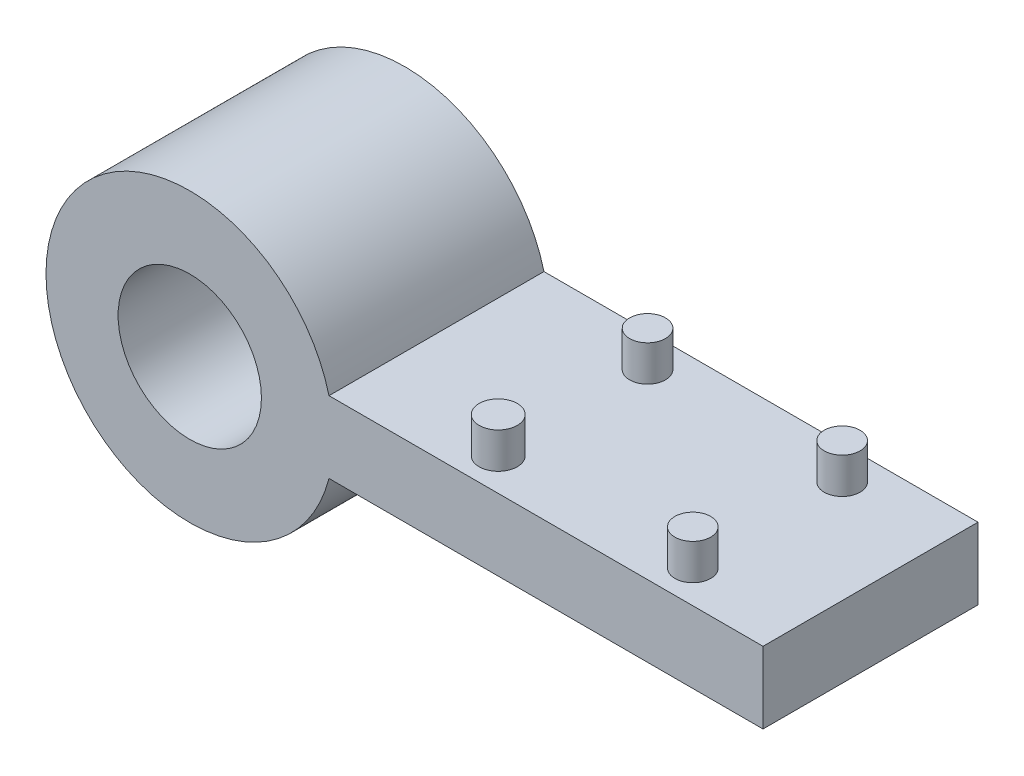
SolidWorks part; units mm, degrees
ref_plane "Front Plane" through (0, 0, 0) normal (0, 0, 1) x (1, 0, 0)
ref_plane "Top Plane" through (0, 0, 0) normal (0, 1, 0) x (1, 0, 0)
ref_plane "Right Plane" through (0, 0, 0) normal (1, 0, 0) x (0, 0, -1)
sketch "Sketch1" plane through (0, 0, -0.4159) normal (0, 1, 0) x (1, 0, 0)
  line L1 (-23.2517, 4.1989) -> (56.7483, 4.1989)
  line L2 (-23.2517, 4.1989) -> (-23.2517, -25.8011)
  line L3 (-23.2517, -25.8011) -> (56.7483, -25.8011)
  line L4 (56.7483, 4.1989) -> (56.7483, -25.8011)
  dimension "D1" = 30
  dimension "D2" = 80
extrude "Boss-Extrude1" add sketch "Sketch1" along normal blind 10
sketch "Sketch2" plane through (0, 0, 25.3852) normal (0, 0, 1) x (1, 0, 0)
  line L0 (-23.2517, 10) -> (-23.2517, 0) construction
  circle A0 centre (-23.2517, 5) radius 20.0629
extrude "Boss-Extrude2" add sketch "Sketch2" against normal blind 30 contours A0
sketch "Sketch4" plane through (0, 0, 25.3852) normal (0, 0, 1) x (1, 0, 0)
  circle A0 centre (-23.2517, 5) radius 10
  arc A1 (-3.8218, 10) -> (-3.8218, 0) centre (-23.2517, 5) ccw construction
  dimension "D1" = 0
extrude "Cut-Extrude1" cut sketch "Sketch4" against normal through all
sketch "Sketch5" plane through (0, 10, 0) normal (0, 1, 0) x (1, 0, 0)
  circle A0 centre (42.4036, -20.8415) radius 2.5
  circle A1 centre (15.2484, -20.8415) radius 2.6587
  circle A2 centre (15.2484, 0) radius 2.5
  circle A3 centre (42.4036, 0) radius 2.5
  point P8 (0, 0)
  point P9 (0, 0)
extrude "Boss-Extrude3" add sketch "Sketch5" along normal blind 5
